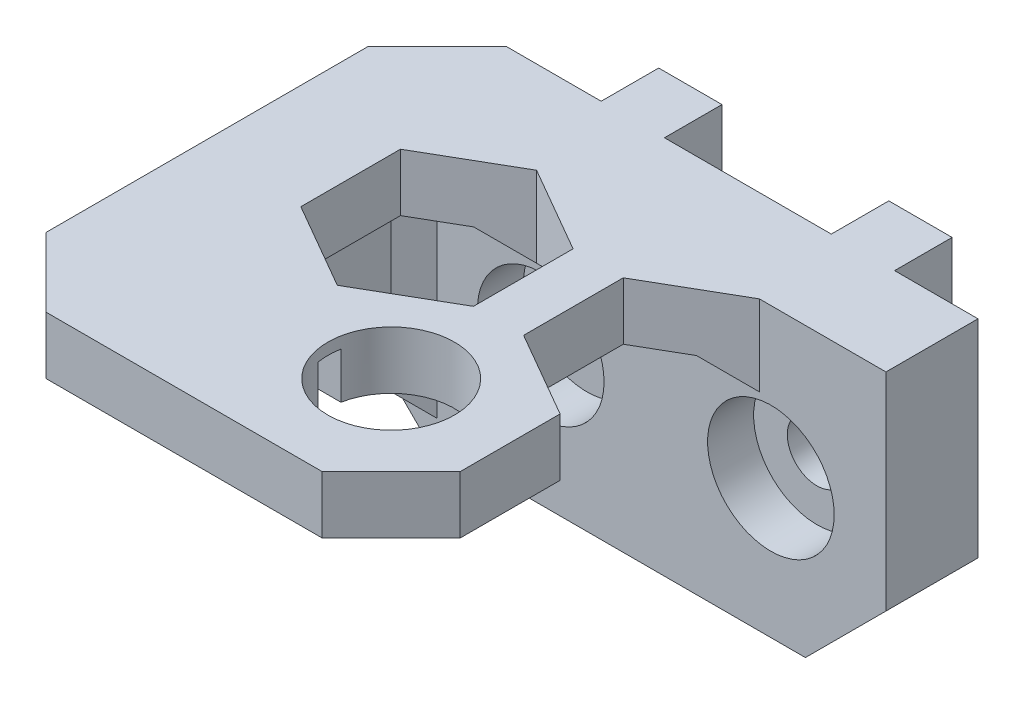
SolidWorks part; units mm, degrees
ref_plane "Front Plane" through (0, 0, 0) normal (0, 0, 1) x (1, 0, 0)
ref_plane "Top Plane" through (0, 0, 0) normal (0, 1, 0) x (1, 0, 0)
ref_plane "Right Plane" through (0, 0, 0) normal (1, 0, 0) x (0, 0, -1)
sketch "Sketch1" plane through (0, 0, 0) normal (0, 1, 0) x (1, 0, 0)
  line L0 (20, 20) -> (20, 12)
  line L1 (-27, 20) -> (20, 20)
  line L2 (-27, 20) -> (-27, -20)
  line L3 (-27, -20) -> (9, -20)
  line L5 (-27, 20) -> (27, -20) construction
  line L6 (-27, -20) -> (27, 20) construction
  line L9 (20, 12) -> (9, 12)
  line L10 (9, -20) -> (9, 12)
  point P0 (0, 0)
  dimension "D1" = 40
  dimension "D2" = 54
  dimension "D3" = 8
  dimension "D5" = 11
  dimension "D6" = 47
extrude "Boss-Extrude1" add sketch "Sketch1" along normal blind 5
sketch "Sketch3" plane through (0, 0, -20) normal (0, 0, -1) x (-1, 0, 0)
  line L0 (27, 5) -> (27, 0) construction
  line L1 (-20, 5) -> (27, 5)
  line L2 (-20, 5) -> (-20, -20)
  line L3 (-20, -20) -> (27, -20)
  line L4 (27, 5) -> (27, -20)
  line L5 (-20, 5) -> (-20, 0) construction
  dimension "D1" = 25
extrude "Boss-Extrude2" add sketch "Sketch3" against normal blind 8
sketch "Sketch9" plane through (-27, 0, 0) normal (-1, 0, 0) x (0, 0, 1)
  line L0 (-12, -18) -> (6, 0)
  line L1 (-12, -20) -> (-12, 0) construction
  line L2 (-12, 0) -> (20, 0) construction
  dimension "D1" = 18
  dimension "D2" = 18
rib "Rib2" sketch "Sketch9" sketch "Sketch9" thickness 6 extrusion direction parallel to sketch draft on no parameters "D1"=6
sketch "Sketch2" plane through (0, 5, 0) normal (0, 1, 0) x (1, 0, 0)
  line L0 (9, -20) -> (9, 12) construction
  line L1 (9, -5.3205) -> (16.5, -0.9904)
  line L2 (16.5, -0.9904) -> (16.5, 7.6699)
  line L3 (-27, 20) -> (-27, -20) construction
  line L4 (16.5, 7.6699) -> (9, 12)
  line L5 (20, 20) -> (-27, 20) construction
  line L6 (9, 12) -> (1.5, 7.6699)
  line L7 (1.5, 7.6699) -> (1.5, -0.9904)
  line L8 (1.5, -0.9904) -> (9, -5.3205)
  line L10 (-10.3622, -5.3205) -> (-2.8622, -0.9904)
  line L11 (-2.8622, -0.9904) -> (-2.8622, 7.6699)
  line L12 (-2.8622, 7.6699) -> (-10.3622, 12)
  line L13 (-10.3622, 12) -> (-17.8622, 7.6699)
  line L14 (-17.8622, 7.6699) -> (-17.8622, -0.9904)
  line L15 (-17.8622, -0.9904) -> (-10.3622, -5.3205)
  circle A0 centre (-1, -10) radius 5.5
  circle A1 centre (-18.5, -10) radius 4.2
  circle A2 centre (9, 3.3397) radius 7.5 construction
  circle A3 centre (-10.3622, 3.3397) radius 7.5 construction
  dimension "D1" = 11
  dimension "D2" = 8.4
  dimension "D5" = 15
  dimension "D3" = 17.5
  dimension "D7" = 26
  dimension "D8" = 30
extrude "Cut-Extrude1" cut sketch "Sketch2" against normal blind 5
sketch "Sketch4" plane through (0, 0, -12) normal (0, 0, 1) x (1, 0, 0)
  line L0 (-27, 5) -> (-27, -20) construction
  line L1 (20, 5) -> (-27, 5) construction
  circle A0 centre (-10, -8) radius 2.575
  circle A1 centre (10, -8) radius 2.575
  dimension "D3" = 13
  dimension "D4" = 5.15
  dimension "D1" = 20
  dimension "D2" = 17
extrude "Cut-Extrude2" cut sketch "Sketch4" against normal blind 8
sketch "Sketch11" plane through (0, 5, 0) normal (0, 1, 0) x (1, 0, 0)
  line L0 (-27, 20) -> (-27, -20) construction
  line L1 (-12.75, 20) -> (-7.25, 20)
  line L2 (-12.75, 20) -> (-12.75, 25)
  line L3 (-12.75, 25) -> (-7.25, 25)
  line L4 (-7.25, 20) -> (-7.25, 25)
  line L5 (20, 20) -> (-27, 20) construction
  line L6 (7.25, 20) -> (12.75, 20)
  line L7 (7.25, 20) -> (7.25, 25)
  line L8 (7.25, 25) -> (12.75, 25)
  line L9 (12.75, 20) -> (12.75, 25)
  point P16 (-10, 25)
  point P19 (10, 25)
  dimension "D1" = 5
  dimension "D2" = 5.5
  dimension "D3" = 20
  dimension "D4" = 17
extrude "Boss-Extrude5" add sketch "Sketch11" against normal blind 7
sketch "Sketch12" plane through (0, 5, 0) normal (0, 1, 0) x (1, 0, 0)
  circle A0 centre (-18.5, -10) radius 4.9411
extrude "Boss-Extrude6" add sketch "Sketch12" against normal blind 1
sketch "Sketch7" plane through (0, 0, -12) normal (0, 0, 1) x (1, 0, 0)
  circle A0 centre (-10, -8) radius 5.5
  circle A1 centre (10, -8) radius 5.5
  dimension "D1" = 11
extrude "Cut-Extrude3" cut sketch "Sketch7" against normal blind 4
sketch "Sketch10" plane through (0, 0, 0) normal (0, -1, 0) x (1, 0, 0)
  line L1 (-16.1431, 10.9653) -> (-5.0831, 10.9653)
  line L2 (-16.1431, 10.9653) -> (-16.1431, 8.9653)
  line L3 (-16.1431, 8.9653) -> (-5.0831, 8.9653)
  line L4 (-5.0831, 10.9653) -> (-5.0831, 8.9653)
  line L5 (-16.1431, 10.9653) -> (-5.0831, 8.9653) construction
  line L6 (-16.1431, 8.9653) -> (-5.0831, 10.9653) construction
  point P0 (-10.6131, 9.9653)
  dimension "D1" = 2
extrude "Cut-Extrude4" cut sketch "Sketch10" against normal blind 4
chamfer "Chamfer1" distance 6 angle 45 3 edges at (9, 2.5, 20) (-27, 2.5, 20) (-27, -7.5, -20)
chamfer "Chamfer2" distance 7 angle 45 2 edges at (-27, -20, -13) (20, -20, -16)
chamfer "Chamfer4" distance 2 angle 45 4 edges at (-0.6811, 0, -12) (-15.6811, 0, -12) (-21, 0, -3) (-21, -9, -12)
pattern_linear "LPattern1" count 2 spacing 18 along (0, -1, 0) of "Boss-Extrude5"
chamfer "Chamfer5" distance 2 angle 45 2 edges at (-10, -2, -25) (10, -2, -25)
chamfer "Chamfer6" distance 5 angle 45 2 edges at (-10, -13, -25) (10, -13, -25)
mirror "Mirror1" [suppressed]
delete or keep bodies "Body-Delete/Keep 1" [suppressed] type delete bodies bodies 108
